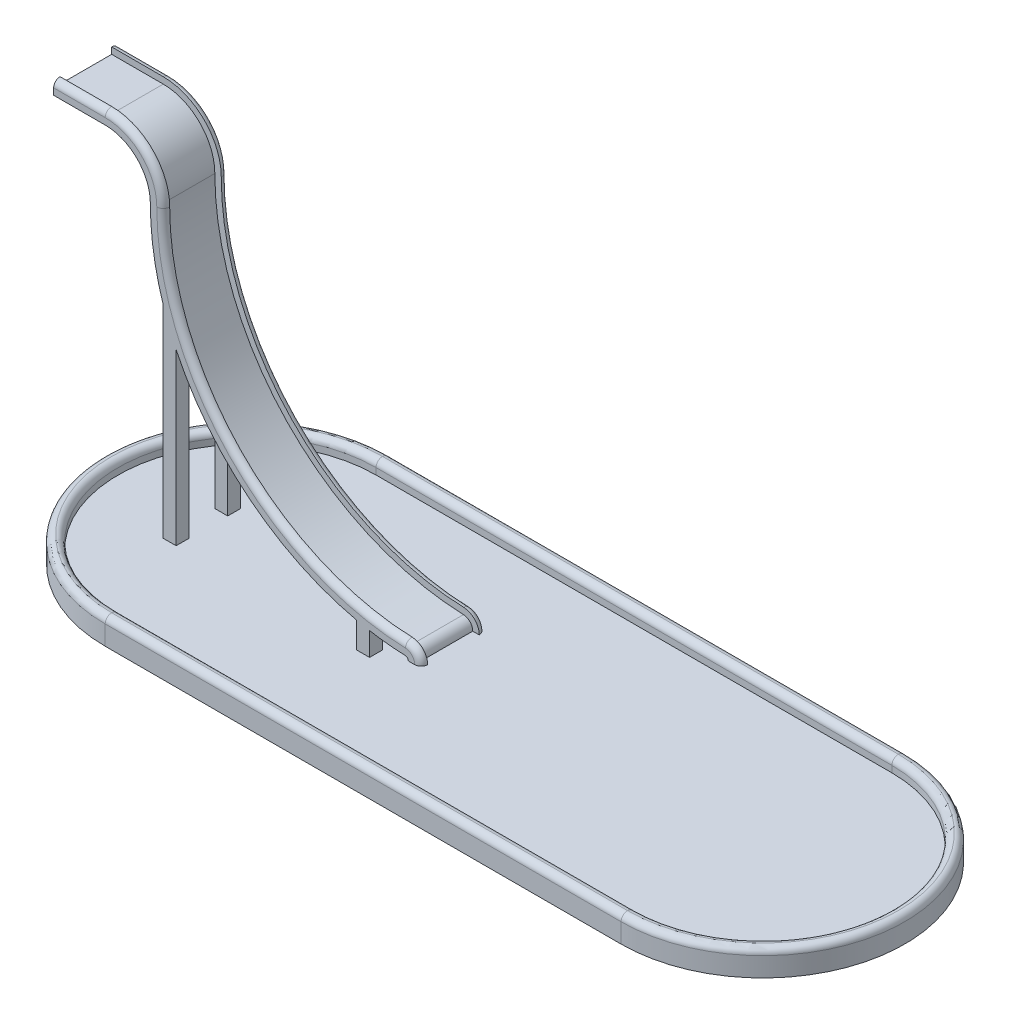
SolidWorks part; units mm, degrees
ref_plane "Спереди" through (0, 0, 0) normal (0, 0, 1) x (1, 0, 0)
ref_plane "Сверху" through (0, 0, 0) normal (0, 1, 0) x (1, 0, 0)
ref_plane "Справа" through (0, 0, 0) normal (1, 0, 0) x (0, 0, -1)
sketch "Эскиз1" plane through (0, 0, 0) normal (0, 1, 0) x (1, 0, 0)
  line L0 (-200, 0) -> (200, 0) construction
  line L1 (-200, 100) -> (200, 100)
  line L2 (-200, -100) -> (200, -100)
  line L3 (-200, 110) -> (200, 110)
  line L4 (-200, -110) -> (200, -110)
  line L5 (-200, 0) -> (200, 0) construction
  line L6 (-244, 15) -> (-240, 15)
  line L7 (-244, 15) -> (-244, 21)
  line L8 (-244, 21) -> (-240, 21)
  line L9 (-240, 15) -> (-240, 21)
  line L10 (-300, 0) -> (300, 0) construction
  line L11 (-244, -15) -> (-244, -21)
  line L12 (-244, -15) -> (-240, -15)
  line L13 (-240, -15) -> (-240, -21)
  line L14 (-244, -21) -> (-240, -21)
  arc A0 (-200, 100) -> (-200, -100) centre (-200, 0) ccw
  arc A1 (200, -100) -> (200, 100) centre (200, 0) ccw
  arc A2 (200, -110) -> (200, 110) centre (200, 0) ccw
  arc A3 (-200, 110) -> (-200, -110) centre (-200, 0) ccw
  point P2 (0, 0)
  dimension "D7" = 400
  dimension "D2" = 15
  dimension "D3" = 4
  dimension "D4" = 40
  dimension "D5" = 6
  dimension "D6" = 100
  dimension "D1" = 10
extrude "Бобышка-Вытянуть1" add sketch "Эскиз1" along normal blind 10 contours L2 A1 L1 A0 L9 L6 L7 L8 L14 L11 L12 L13 region at (0.1043, 0, 0)
extrude "Бобышка-Вытянуть2" add sketch "Эскиз1<3>" along normal blind 20 contours L3 A3 L4 A2 A1 L2 A0 L1 region at (0, 0, -103.4212)
sketch "Эскиз1<3>" plane through (0, 0, 0) normal (0, 1, 0) x (1, 0, 0) same geometry as "Эскиз1"
extrude "Бобышка-Вытянуть3" add sketch "Эскиз1<4>" along normal blind 10 contours L13 L14 L11 L12 | L9 L8 L7 L6
sketch "Эскиз1<4>" plane through (0, 0, 0) normal (0, 1, 0) x (1, 0, 0) same geometry as "Эскиз1"
fillet "Скругление1" radius 5 8 edges at (310, 20, 0) (0, 20, 110) (-310, 20, 0) (0, 20, -110) (0, 20, -100) (-300, 20, 0) (0, 20, 100) (300, 20, 0)
sketch "Эскиз2" plane through (0, 0, 0) normal (0, 0, 1) x (1, 0, 0)
  line L0 (-310, 0) -> (310, 0) construction
  line L1 (-45, 230) -> (-320, 230) construction
  line L2 (-45, 230) -> (-45, 15) construction
  line L3 (-285, 270) -> (-325, 270)
  line L4 (-52.5, 22.6356) -> (-45, 22.6356) construction
  line L5 (-200, 15) -> (-310, 15) construction
  line L6 (-285, 275) -> (-325, 275)
  line L7 (-285, 265) -> (-325, 265)
  line L8 (-50, 22.6356) -> (-40, 22.6356)
  line L9 (-325, 275) -> (-325, 265)
  line L10 (-310, 15) -> (-310, 0) construction
  line L11 (-240, 0) -> (-240, 166.7544)
  line L12 (-230, 0) -> (-230, 141.6824)
  line L13 (-80, 28.0099) -> (-80, 0)
  line L14 (-90, 30) -> (-90, 0)
  line L15 (-240, 0) -> (-230, 0)
  line L16 (-90, 0) -> (-80, 0)
  arc A0 (-245, 230) -> (-52.2289, 30.1307) centre (-45, 230) ccw
  arc A1 (-245, 230) -> (-285, 270) centre (-285, 230) ccw
  arc A2 (-45, 22.6356) -> (-52.2289, 30.1307) centre (-52.5, 22.6356) ccw
  arc A3 (-240, 230) -> (-285, 275) centre (-285, 230) ccw
  arc A4 (-240, 230) -> (-52.0482, 35.1274) centre (-45, 230) ccw
  arc A5 (-40, 22.6356) -> (-52.0482, 35.1274) centre (-52.5, 22.6356) ccw
  arc A6 (-250, 230) -> (-285, 265) centre (-285, 230) ccw
  arc A7 (-250, 230) -> (-52.4096, 25.134) centre (-45, 230) ccw
  arc A8 (-50, 22.6356) -> (-52.4096, 25.134) centre (-52.5, 22.6356) ccw
  point P4 (0, 0)
  dimension "D1" = 400
  dimension "D4" = 80
  dimension "D6" = 15
  dimension "D2" = 230
  dimension "D3" = 45
  dimension "D5" = 40
  dimension "D9" = 230
  dimension "D10" = 10
  dimension "D11" = 10
  dimension "D12" = 80
  dimension "D7" = 5
  dimension "D8" = 5
extrude "Бобышка-Вытянуть4" add sketch "Эскиз2" along normal mid plane 50 contours A8 L8 A2 A0 A1 L3 L9 L7 A6 A7 region at (-259.3576, 255.6424, 0)
extrude "Бобышка-Вытянуть5" add sketch "Эскиз2<4>" against normal blind 5 from vertex contours L8 A5 A4 A3 L6 L9 L3 A1 A0 A2 region at (-305, 273.8067, 0) starting at point (-52.2289, 30.1307, 25)
sketch "Эскиз2<4>" plane through (0, 0, 0) normal (0, 0, 1) x (1, 0, 0) same geometry as "Эскиз2"
extrude "Бобышка-Вытянуть6" add sketch "Эскиз2<5>" along normal blind 5 from vertex contours L8 A5 A4 A3 L6 L9 L3 A1 A0 A2 region at (-305, 273.8067, 0) starting at point (-52.2289, 30.1307, -25)
sketch "Эскиз2<5>" plane through (0, 0, 0) normal (0, 0, 1) x (1, 0, 0) same geometry as "Эскиз2"
extrude "Бобышка-Вытянуть7" add sketch "Эскиз2<8>" along normal blind 10 from offset 15 contours A7 L11 L15 L12 | A7 L14 L16 L13 region at (-235.1353, 76.8779, 0) region at (-85.0573, 14.4866, 0)
sketch "Эскиз2<8>" plane through (0, 0, 0) normal (0, 0, 1) x (1, 0, 0) same geometry as "Эскиз2"
extrude "Бобышка-Вытянуть8" add sketch "Эскиз2<9>" along normal blind 10 from offset 25 contours A7 L11 L15 L12 | A7 L14 L16 L13 region at (-235.1353, 76.8779, 0) region at (-85.0573, 14.4866, 0) offset against normal yes
sketch "Эскиз2<9>" plane through (0, 0, 0) normal (0, 0, 1) x (1, 0, 0) same geometry as "Эскиз2"
fillet "Скругление2" radius 5 8 edges at (-305, 275, -25) (-253.1802, 261.8198, -25) (-43.5028, 31.3132, -25) (-305, 275, 25) (-253.1802, 261.8198, 25) (-43.5028, 31.3132, 25) (-185.3556, 94.629, -25) (-185.3556, 94.629, 25)
equation "\"D11@Эскиз2\"=\"D10@Эскиз2\""
